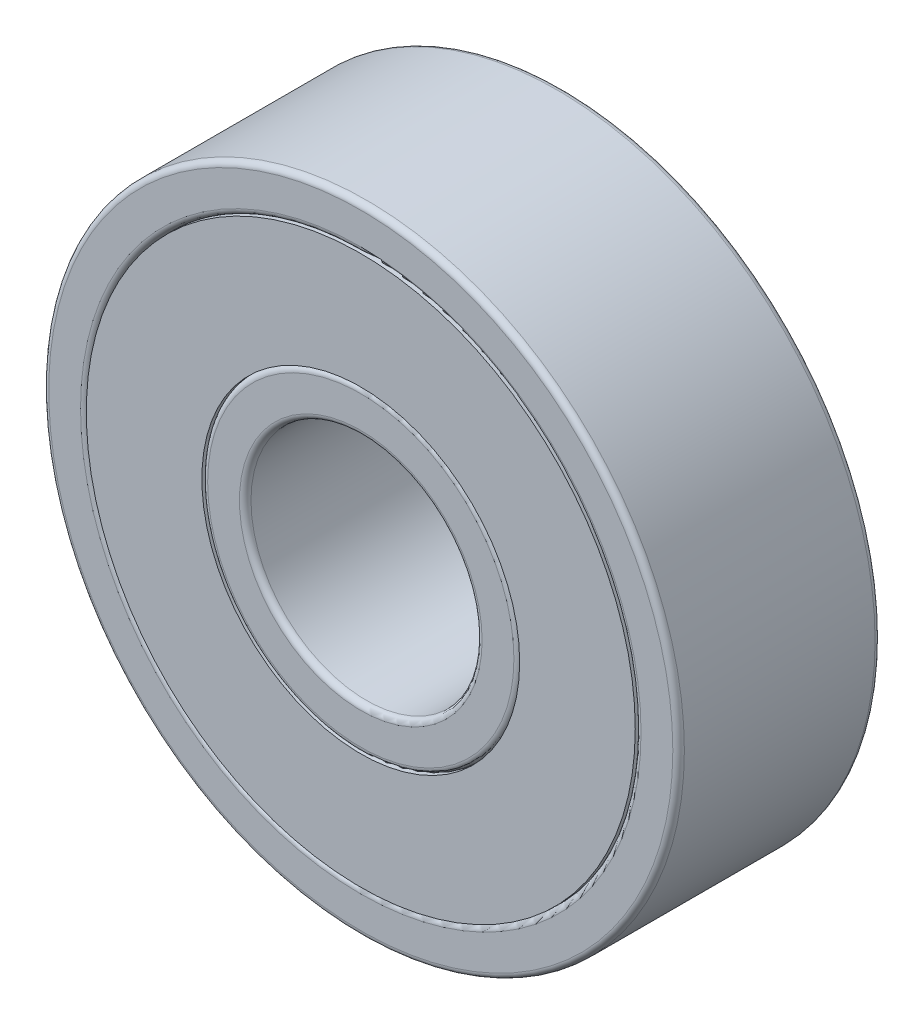
SolidWorks part; units mm, degrees
ref_plane "Front Plane" through (0, 0, 0) normal (0, 0, 1) x (1, 0, 0)
ref_plane "Top Plane" through (0, 0, 0) normal (0, 1, 0) x (1, 0, 0)
ref_plane "Right Plane" through (0, 0, 0) normal (1, 0, 0) x (0, 0, -1)
sketch "Sketch1" plane through (0, 0, 0) normal (0, 0, 1) x (1, 0, 0)
  circle A0 centre (0, 0) radius 11
  circle A1 centre (0, 0) radius 9.5
  circle A2 centre (0, 0) radius 4
  circle A3 centre (0, 0) radius 5.5
  dimension "D1" = 22
  dimension "D3" = 8
  dimension "D2" = 1.5
  dimension "D4" = 1.5
extrude "Boss-Extrude1" add sketch "Sketch1" along normal blind 7 contours A0 A1 | A3 A2 region at (-10.6889, 0, 0) region at (-5.3444, 0, 0)
extrude "Boss-Extrude2" add sketch "Sketch1<3>" along normal blind 7 separate body contours A1 A3 region at (-9.2313, 0, 0)
sketch "Sketch1<3>" plane through (0, 0, 0) normal (0, 0, 1) x (1, 0, 0) same geometry as "Sketch1"
fillet "Fillet1" radius 0.2 4 edges at (11, 0, 0) (9.5, 0, 0) (11, 0, 7) (9.5, 0, 7)
fillet "Fillet2" radius 0.2 4 edges at (5.5, 0, 0) (4, 0, 0) (5.5, 0, 7) (4, 0, 7)
equation "\"d-out\"= 22"
equation "\"d-in\"= 8"
equation "\"t\"= 1.5"
equation "\"b\"= 7"
equation "\"D1@Boss-Extrude2\"=\"b\""
equation "\"D1@Sketch1\"=\"d-out\""
equation "\"D3@Sketch1\"=\"d-in\""
equation "\"D4@Sketch1\"=\"t\""
equation "\"D2@Sketch1\"=\"t\""
equation "\"D1@Boss-Extrude1\"=\"b\""
